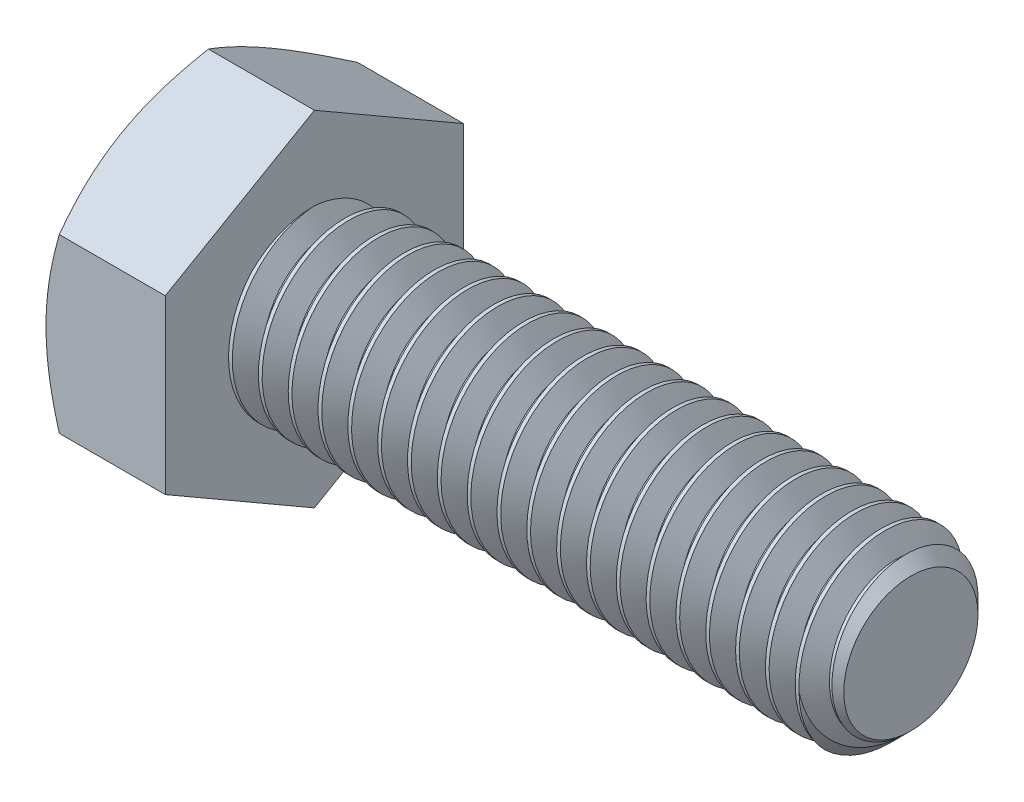
SolidWorks part; units mm, degrees
material "Brass"
ref_plane "Front Plane" through (0, 0, 0) normal (0, 0, 1) x (1, 0, 0)
ref_plane "Top Plane" through (0, 0, 0) normal (0, 1, 0) x (1, 0, 0)
ref_plane "Right Plane" through (0, 0, 0) normal (1, 0, 0) x (0, 0, -1)
sketch "Sketch1" plane through (0, 0, 0) normal (0, 0, 1) x (1, 0, 0)
  line L0 (-12, 0) -> (12, 0) construction
  line L1 (-8, 5) -> (-8, -5) construction
  line L2 (-12, 5) -> (-12, -5) construction
  line L3 (12, 3) -> (12, -3) construction
  point P8 (8.5, -3)
  dimension "Thread Dia" = 6
  dimension "Hex" = 10
  dimension "Head Ht" = 4
  dimension "Length" = 20
  dimension "D1" = 3.5
ref_plane "Plane2" through (12, 0, 0) normal (1, 0, 0) x (0, 0, -1)
sketch "Sketch2" plane through (12, 0, 0) normal (1, 0, 0) x (0, 0, -1)
  circle A0 centre (0, 0) radius 3
extrude "Boss-Extrude1" add sketch "Sketch2" against normal up to vertex (20 mm away) up to point (-8, -5, 0)
sketch "Sketch4" plane through (12, 0, 0) normal (1, 0, 0) x (0, 0, -1)
  circle A1 centre (0, 0) radius 3
  circle A2 centre (0, 0) radius 3
  dimension "D1" = 0
curve "Helix/Spiral1" pitch 1 height 21 turns 21 parameters "Pitch"=1
chamfer "Chamfer1" distance 0.75 angle 45 1 edges at (12, 0, -3)
sketch "Sketch5" plane through (0, 0, 0) normal (0, 0, 1) x (1, 0, 0)
  line L0 (12, 3) -> (12.375, 2.3505)
  line L1 (12.375, 2.3505) -> (12.5, 2.3505)
  line L2 (12.5, 2.3505) -> (12.875, 3)
  line L3 (12, 3) -> (12.875, 3)
  line L4 (12.4375, 2.3505) -> (12.4375, 3) construction
  line L5 (12.1875, 2.6752) -> (12.6875, 2.6752) construction
  line L6 (12, -3) -> (12, 3) construction
  dimension "D1" = 60
  dimension "D2" = 0.125
  dimension "D3" = 0.5
sweep "Cut-Sweep1" cut profiles "Sketch5" path "Helix/Spiral1" align with end faces yes
sketch "Sketch3" plane through (-8, 0, 0) normal (-1, 0, 0) x (0, 0, 1)
  line L0 (0, 5) -> (0, -5) construction
  line L1 (-5, -2.8868) -> (0, -5.7735)
  line L2 (0, -5.7735) -> (5, -2.8868)
  line L3 (5, -2.8868) -> (5, 2.8868)
  line L4 (5, 2.8868) -> (0, 5.7735)
  line L5 (0, 5.7735) -> (-5, 2.8868)
  line L6 (-5, 2.8868) -> (-5, -2.8868)
  circle A0 centre (0, 0) radius 5 construction
extrude "Boss-Extrude2" add sketch "Sketch3" along normal up to vertex (4 mm away) up to point (-12, -5, 0)
sketch "Sketch6" plane through (-12, 0, 0) normal (-1, 0, 0) x (0, 0, 1)
  circle A0 centre (0, 0) radius 5 construction
  circle A1 centre (0, 0) radius 5
extrude "Cut-Extrude1" cut sketch "Sketch6" against normal through all draft 60 flip side to cut
sketch "Sketch7" plane through (-12, 0, 0) normal (-1, 0, 0) x (0, 0, 1)
  line L0 (0, 0) -> (0, 5) construction
  line L2 (0, 5) -> (0, -5) construction
  line L3 (-4.3301, 2.5) -> (4.3301, 2.5) construction
  circle A1 centre (0, 0) radius 5 construction
  text T0 "10.9" font "Arial" height in points 6
  point P8 (0, 2.5)
extrude "Cut-Extrude2" cut sketch "Sketch7" against normal blind 0.25
sketch "Sketch9" plane through (0, 0, 0) normal (0, 0, 1) x (1, 0, 0)
  line L0 (-8, 3) -> (-8, 0)
  line L1 (-8, 0) -> (-39, 0)
  line L2 (-39, 0) -> (-42, 3)
  line L3 (-42, 3) -> (-8, 3)
  line L4 (-12, 0) -> (12, 0) construction
  line L5 (-8, 5) -> (-8, -5) construction
  line L6 (12, 3) -> (12, -3) construction
  dimension "D1" = 45
  dimension "MinThreadLg" = 54
revolve "Revolve1" [suppressed] add sketch "Sketch9" angle 360 about L1
equation "\"D2@Sketch5\" = \"Pitch@Helix/Spiral1\"*.125"
equation "\"D3@Sketch5\" = \"Pitch@Helix/Spiral1\"*.50"
equation "\"D3@Helix/Spiral1\" = \"Length@Sketch1\"+\"Pitch@Helix/Spiral1\""
equation "\"D1@Chamfer1\" = \"Pitch@Helix/Spiral1\"*.750"
equation "\"D1@Sketch1\" = \"Pitch@Helix/Spiral1\"*3.50"
